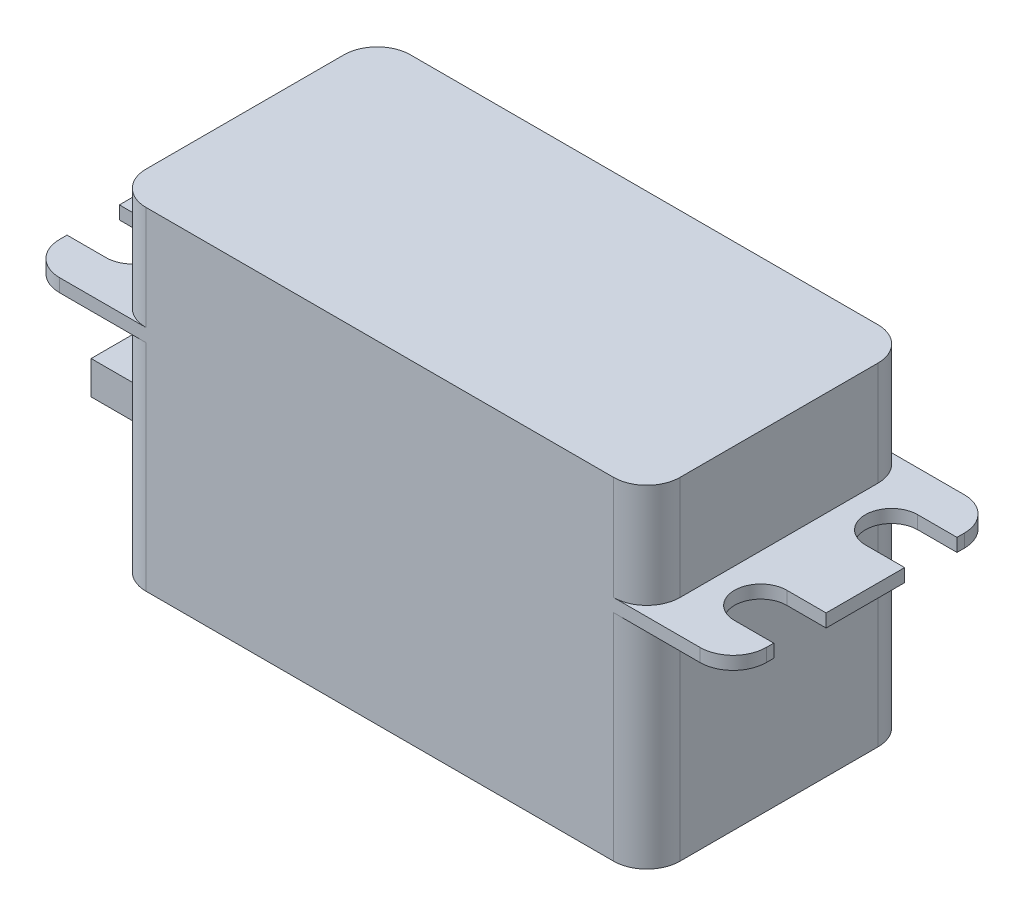
SolidWorks part; units mm, degrees
ref_plane "Front Plane" through (0, 0, 0) normal (0, 0, 1) x (1, 0, 0)
ref_plane "Top Plane" through (0, 0, 0) normal (0, 1, 0) x (1, 0, 0)
ref_plane "Right Plane" through (0, 0, 0) normal (1, 0, 0) x (0, 0, -1)
sketch "Sketch1" plane through (0, 0, 0) normal (0, 1, 0) x (1, 0, 0)
  line L0 (-55, 0) -> (55, 0) construction
  line L1 (-24.46, -10.1) -> (24.46, -10.1)
  line L2 (-27, -7.56) -> (-27, 7.56)
  line L3 (-24.46, 10.1) -> (24.46, 10.1)
  line L4 (27, -7.56) -> (27, 7.56)
  line L5 (-27, -10.1) -> (27, 10.1) construction
  line L6 (-27, 10.1) -> (27, -10.1) construction
  line L7 (0, -55) -> (0, 55) construction
  line L8 (24, 3) -> (27, 3)
  line L9 (24, 7) -> (27, 7)
  line L10 (27, 7) -> (27, 3)
  line L11 (24, -3) -> (27, -3)
  line L12 (24, -7) -> (27, -7)
  line L13 (27, -7) -> (27, -3)
  line L14 (-24, 7) -> (-27, 7)
  line L15 (-24, 3) -> (-27, 3)
  line L16 (-27, 3) -> (-27, 7)
  line L17 (-24, -7) -> (-27, -7)
  line L18 (-24, -3) -> (-27, -3)
  line L19 (-27, -3) -> (-27, -7)
  arc A0 (24, 7) -> (24, 3) centre (24, 5) ccw
  arc A1 (24, -7) -> (24, -3) centre (24, -5) cw
  arc A2 (-24, -7) -> (-24, -3) centre (-24, -5) ccw
  arc A3 (-24, 7) -> (-24, 3) centre (-24, 5) cw
  arc A4 (-24.46, -10.1) -> (-27, -7.56) centre (-24.46, -7.56) cw
  arc A5 (24.46, -10.1) -> (27, -7.56) centre (24.46, -7.56) ccw
  arc A6 (24.46, 10.1) -> (27, 7.56) centre (24.46, 7.56) cw
  arc A7 (-27, 7.56) -> (-24.46, 10.1) centre (-24.46, 7.56) cw
  point P0 (0, 0)
  dimension "D3" = 4
  dimension "D6" = 2.54
  dimension "D1" = 54
  dimension "D2" = 20.2
  dimension "D4" = 48
  dimension "D5" = 10
extrude "Boss-Extrude1" add sketch "Sketch1" along normal blind 1 contours A7 L2 L14 A3 L15 L18 A2 L17 A4 L1 A5 L4 L12 A1 L11 L8 A0 L9 A6 L3 region at (0, 0, 0)
sketch "Sketch3" plane through (0, 1, 0) normal (0, 1, 0) x (1, 0, 0)
  line L1 (-17.86, -10.1) -> (17.86, -10.1)
  line L2 (-20.4, -7.56) -> (-20.4, 7.56)
  line L3 (-17.86, 10.1) -> (17.86, 10.1)
  line L4 (20.4, -7.56) -> (20.4, 7.56)
  line L5 (-20.4, -10.1) -> (20.4, 10.1) construction
  line L6 (-20.4, 10.1) -> (20.4, -10.1) construction
  arc A0 (-17.86, -10.1) -> (-20.4, -7.56) centre (-17.86, -7.56) cw
  arc A1 (17.86, -10.1) -> (20.4, -7.56) centre (17.86, -7.56) ccw
  arc A2 (17.86, 10.1) -> (20.4, 7.56) centre (17.86, 7.56) cw
  arc A3 (-20.4, 7.56) -> (-17.86, 10.1) centre (-17.86, 7.56) cw
  point P0 (0, 0)
  dimension "D3" = 2.54
  dimension "D1" = 40.8
  dimension "D2" = 20.2
extrude "Boss-Extrude2" add sketch "Sketch3" along normal blind 7.95
sketch "Sketch4" plane through (0, 0, 0) normal (0, -1, 0) x (1, 0, 0)
  line L1 (-17.86, -10.1) -> (17.86, -10.1)
  line L2 (-20.4, -7.56) -> (-20.4, 7.56)
  line L3 (-17.86, 10.1) -> (17.86, 10.1)
  line L4 (20.4, -7.56) -> (20.4, 7.56)
  line L5 (-20.4, -10.1) -> (20.4, 10.1) construction
  line L6 (-20.4, 10.1) -> (20.4, -10.1) construction
  arc A0 (-17.86, -10.1) -> (-20.4, -7.56) centre (-17.86, -7.56) cw
  arc A1 (17.86, -10.1) -> (20.4, -7.56) centre (17.86, -7.56) ccw
  arc A2 (17.86, 10.1) -> (20.4, 7.56) centre (17.86, 7.56) cw
  arc A3 (-20.4, 7.56) -> (-17.86, 10.1) centre (-17.86, 7.56) cw
  point P0 (0, 0)
  dimension "D3" = 2.54
  dimension "D1" = 20.2
  dimension "D2" = 40.8
extrude "Boss-Extrude3" add sketch "Sketch4" along normal blind 16.45
sketch "Sketch5" plane through (-20.4, 0, 0) normal (-1, 0, 0) x (0, 0, 1)
  line L0 (-0.3522, -9.5691) -> (-0.3522, -11.2663)
  line L1 (-3.481, -11.6473) -> (4.139, -11.6473)
  line L2 (-3.481, -11.6473) -> (-3.481, -9.1073)
  line L3 (-3.481, -9.1073) -> (4.139, -9.1073)
  line L4 (4.139, -11.6473) -> (4.139, -9.1073)
  line L5 (-2.8922, -9.5691) -> (-1.2989, -9.5691)
  line L6 (-2.8922, -9.5691) -> (-2.8922, -11.2663)
  line L7 (-2.8922, -11.2663) -> (-1.2989, -11.2663)
  line L8 (-1.2989, -9.5691) -> (-1.2989, -11.2663)
  line L9 (-0.3522, -9.5691) -> (1.2411, -9.5691)
  line L10 (1.2411, -9.5691) -> (1.2411, -11.2663)
  line L11 (-0.3522, -11.2663) -> (1.2411, -11.2663)
  line L12 (2.1878, -9.5691) -> (2.1878, -11.2663)
  line L13 (2.1878, -9.5691) -> (3.7811, -9.5691)
  line L14 (3.7811, -9.5691) -> (3.7811, -11.2663)
  line L15 (2.1878, -11.2663) -> (3.7811, -11.2663)
  dimension "D2" = 2.54
  dimension "D3" = 2.54
  dimension "D4" = 7.62
  dimension "D1" = 3
extrude "Boss-Extrude4" add sketch "Sketch5" along normal blind 7.62
